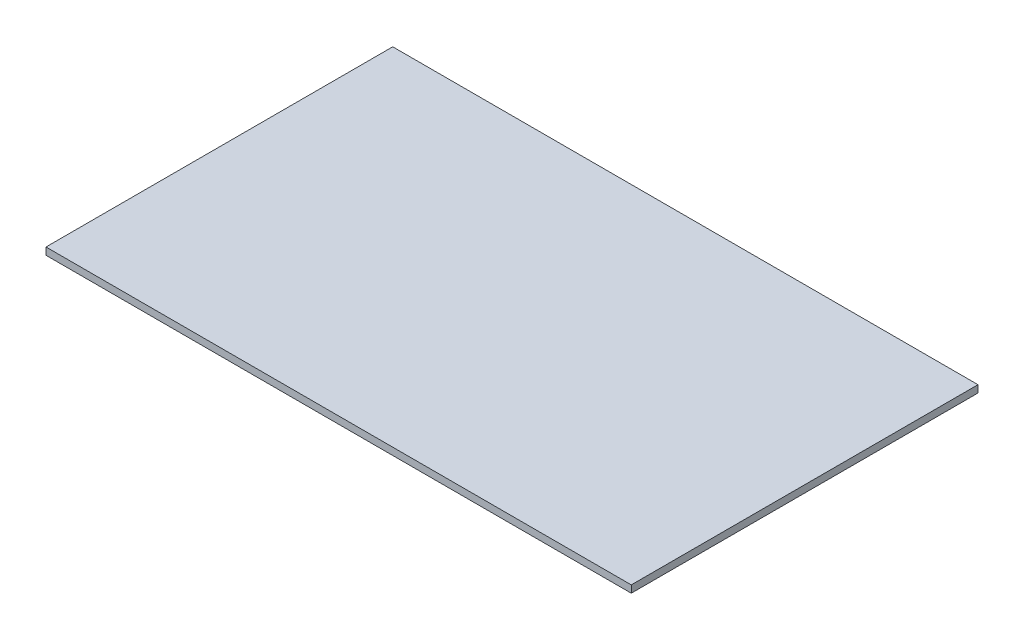
SolidWorks part; units mm, degrees
ref_plane "Front Plane" through (0, 0, 0) normal (0, 0, 1) x (1, 0, 0)
ref_plane "Top Plane" through (0, 0, 0) normal (0, 1, 0) x (1, 0, 0)
ref_plane "Right Plane" through (0, 0, 0) normal (1, 0, 0) x (0, 0, -1)
sketch "Sketch1" plane through (0, 0, 0) normal (0, 1, 0) x (1, 0, 0)
  line L1 (0, 0) -> (514.4775, 0)
  line L2 (0, 0) -> (0, 304.8)
  line L3 (0, 304.8) -> (514.4775, 304.8)
  line L4 (514.4775, 0) -> (514.4775, 304.8)
extrude "Boss-Extrude1" add sketch "Sketch1" along normal blind 6.35
